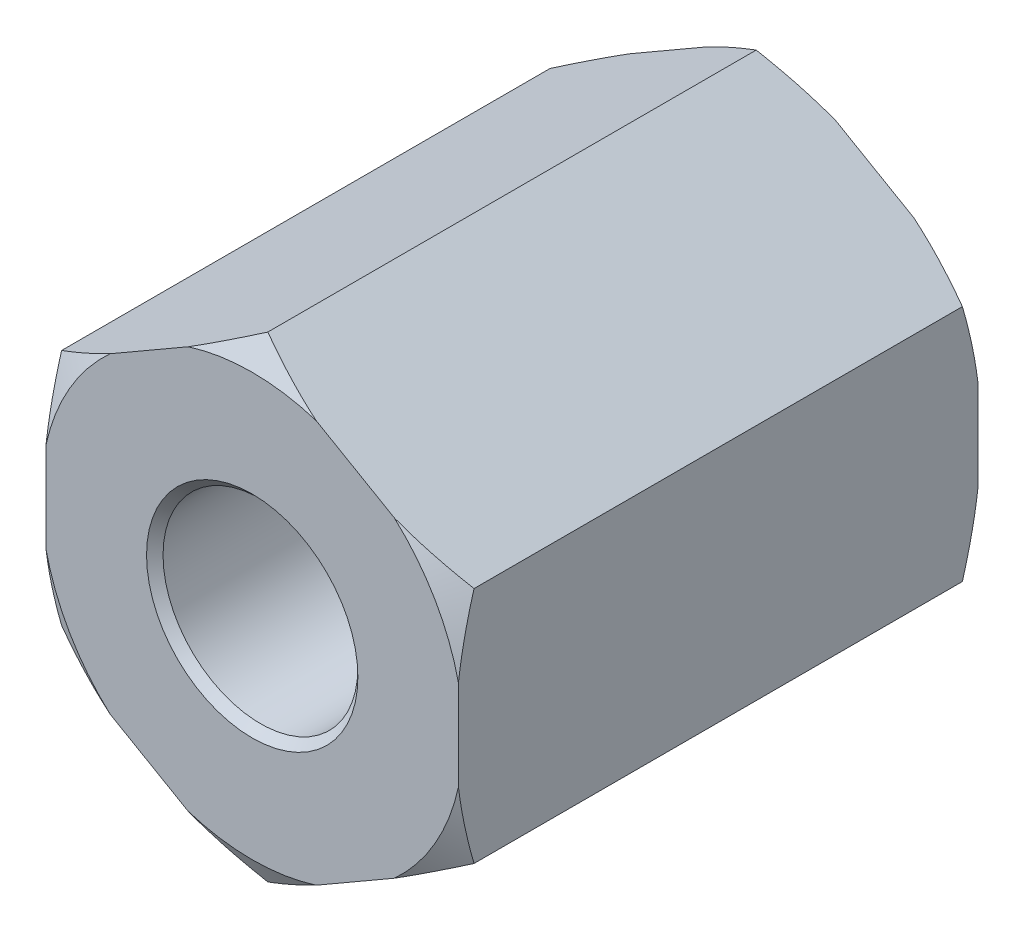
SolidWorks part; units mm, degrees
ref_plane "Front Plane" through (0, 0, 0) normal (0, 0, 1) x (1, 0, 0)
ref_plane "Top Plane" through (0, 0, 0) normal (0, 1, 0) x (1, 0, 0)
ref_plane "Right Plane" through (0, 0, 0) normal (1, 0, 0) x (0, 0, -1)
sketch "Sketch1" plane through (0, 0, 0) normal (0, 0, 1) x (1, 0, 0)
  line L1 (0, 7.5056) -> (-6.5, 3.7528)
  line L2 (-6.5, 3.7528) -> (-6.5, -3.7528)
  line L3 (-6.5, -3.7528) -> (0, -7.5056)
  line L4 (0, -7.5056) -> (6.5, -3.7528)
  line L5 (6.5, -3.7528) -> (6.5, 3.7528)
  line L6 (6.5, 3.7528) -> (0, 7.5056)
  circle A0 centre (0, 0) radius 6.5 construction
  dimension "Hex" = 13
extrude "Extrude1" add sketch "Sketch1" against normal blind 16
sketch "Sketch2" plane through (0, 0, 0) normal (0, 0, 1) x (1, 0, 0)
  circle A0 centre (0, 0) radius 6.5 construction
  circle A1 centre (0, 0) radius 6.5
extrude "Cut-Extrude1" cut sketch "Sketch2" against normal through all draft 60 flip side to cut
sketch "Sketch3" plane through (0, 0, -16) normal (0, 0, -1) x (-1, 0, 0)
  circle A1 centre (0, 0) radius 6.5
  circle A2 centre (0, 0) radius 6.5
  dimension "D1" = 0
extrude "Cut-Extrude2" cut sketch "Sketch3" against normal through all draft 60 flip side to cut
sketch "Sketch4" plane through (0, 0, 0) normal (0, 0, 1) x (1, 0, 0)
  circle A0 centre (0, 0) radius 3
  dimension "Thread Dia" = 6
extrude "Cut-Extrude3" cut sketch "Sketch4" against normal through all
sketch "Sketch7" plane through (0, 0, 0) normal (0, 0, 1) x (1, 0, 0)
  circle A4 centre (0, 0) radius 3.254
  circle A5 centre (0, 0) radius 3.254
  dimension "D1" = 0.254
sketch "Sketch8" plane through (0, 0, -16) normal (0, 0, -1) x (-1, 0, 0)
  circle A1 centre (0, 0) radius 3.254
  circle A2 centre (0, 0) radius 3.254 construction
sketch "Sketch5" plane through (0, 0, 0) normal (0, 0, 1) x (1, 0, 0)
  circle A0 centre (0, 0) radius 3 construction
  circle A1 centre (0, 0) radius 3
curve "Helix/Spiral1" pitch 1 height 17 radius 3 centre (0, 0, 0) axis (0, 0, -1) start towards (0, 1, 0) parameters "pitch"=1
sketch "Sketch9" plane through (0, 0, 0) normal (1, 0, 0) x (0, 0, -1)
  line L0 (-0.5, 3) -> (-0.375, 3)
  line L1 (-0.375, 3) -> (0, 2.3505)
  line L2 (-0.5, 3) -> (-0.875, 2.3505)
  line L3 (-0.875, 2.3505) -> (0, 2.3505)
  line L4 (-0.4375, 3) -> (-0.4375, 2.3505) construction
  line L5 (-0.6875, 2.6752) -> (-0.1875, 2.6752) construction
  line L7 (0, 2.3505) -> (0, 3) construction
  line L8 (0, 3) -> (0, -3) construction
  dimension "D1" = 0.125
  dimension "D2" = 0.5
  dimension "D3" = 60
sketch "Sketch12" plane through (0, 0, 0) normal (0, 0, 1) x (1, 0, 0)
  circle A0 centre (0, 0) radius 2.3505
  circle A1 centre (0, 0) radius 3 construction
  circle A2 centre (0, 0) radius 3
extrude "Extrude2" add sketch "Sketch12" against normal up to surface (16 mm away) up to face at (3, 0, -16)
sweep "Cut-Sweep1" cut profiles "Sketch9" path "Helix/Spiral1" align with end faces yes
extrude "Cut-Extrude6" cut sketch "Sketch7" against normal through all draft 45
extrude "Cut-Extrude7" cut sketch "Sketch8" against normal through all draft 45
sketch "Sketch13" plane through (0, 0, 0) normal (0, 0, 1) x (1, 0, 0)
  circle A0 centre (0, 0) radius 3
  dimension "D1" = 6
extrude "Cut-Extrude8" cut sketch "Sketch13" against normal through all
sketch "Sketch14" plane through (0, 0, 0) normal (0, 0, 1) x (1, 0, 0)
  line L0 (0, 0) -> (0, 7.5056) construction
  line L1 (0, 7.3323) -> (-6.35, 3.6662)
  line L2 (-6.35, 3.6662) -> (-6.35, -3.6662)
  line L3 (-6.35, -3.6662) -> (0, -7.3323)
  line L4 (0, -7.3323) -> (6.35, -3.6662)
  line L5 (6.35, -3.6662) -> (6.35, 3.6662)
  line L6 (6.35, 3.6662) -> (0, 7.3323)
  circle A0 centre (0, 0) radius 6.35 construction
  dimension "D1" = 12.7
extrude "Cut-Extrude9" cut sketch "Sketch14" against normal through all flip side to cut
equation "\"D2@Sketch9\" = \"pitch@Helix/Spiral1\"*.5"
equation "\"D3@Helix/Spiral1\" = \"pitch@Helix/Spiral1\"+\"Height@Extrude1\""
equation "\"D1@Sketch9\" = \"pitch@Helix/Spiral1\"*.125"
